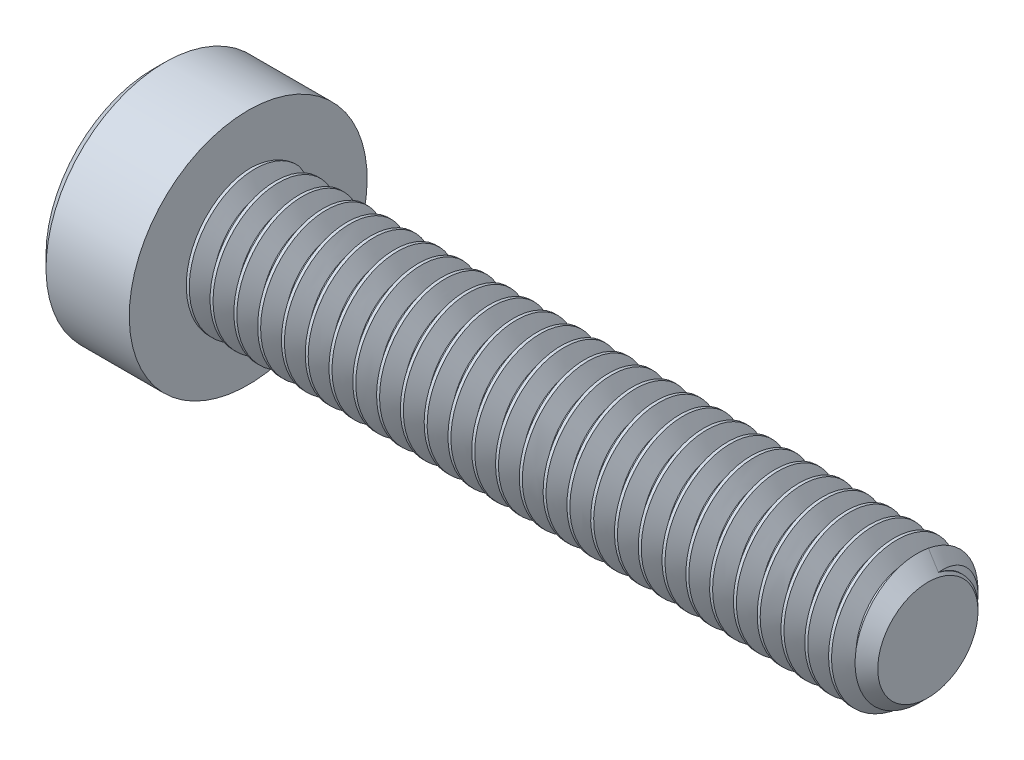
SolidWorks part; units mm, degrees
ref_plane "Front Plane" through (0, 0, 0) normal (0, 0, 1) x (1, 0, 0)
ref_plane "Top Plane" through (0, 0, 0) normal (0, 1, 0) x (1, 0, 0)
ref_plane "Right Plane" through (0, 0, 0) normal (1, 0, 0) x (0, 0, -1)
sketch "Sketch1" plane through (0, 0, 0) normal (0, 0, 1) x (1, 0, 0)
  line L0 (10, 0) -> (-10, 0) construction
  line L1 (10, 2) -> (10, -2) construction
  line L2 (-10, 3.5) -> (-10, -3.5) construction
  line L3 (-10, 3.5) -> (-12.45, 3.5) construction
  line L4 (-12.45, 3.5) -> (-12.8, 3.15) construction
  line L5 (-12.8, 3.15) -> (-12.8, -3.15) construction
  line L6 (-12.8, -3.15) -> (-12.45, -3.5) construction
  line L7 (-12.45, -3.5) -> (-10, -3.5) construction
  point P7 (-10.38, 0)
  point P12 (7.2, -2)
  dimension "D1" = 45
  dimension "Dec." = 4
  dimension "Length" = 20
  dimension "Head Dia" = 7
  dimension "Head Height" = 2.8
  dimension "Hex Depth" = 2.42
  dimension "Chamfer" = 0.35
  dimension "D2" = 2.8
ref_plane "Plane1" through (10, 0, 0) normal (1, 0, 0) x (0, 0, -1)
ref_plane "Plane2" through (-12.8, 0, 0) normal (1, 0, 0) x (0, 0, -1)
sketch "Sketch2" plane through (10, 0, 0) normal (1, 0, 0) x (0, 0, -1)
  circle A0 centre (0, 0) radius 2
extrude "Boss-Extrude1" add sketch "Sketch2" against normal up to vertex (20 mm away) up to point (-10, 0, 0)
sketch "Sketch3" plane through (10, 0, 0) normal (1, 0, 0) x (0, 0, -1)
  circle A0 centre (0, 0) radius 2 construction
  circle A1 centre (0, 0) radius 2
curve "Helix/Spiral1" pitch 0.7 height 20.6688 turns 29.5268 parameters "Pitch"=0.7
chamfer "Chamfer1" distance 0.525 angle 45 1 edges at (10, 0, -2)
sketch "Sketch5" plane through (0, 0, 0) normal (0, 0, 1) x (1, 0, 0)
  line L0 (9.6938, 2) -> (10.3062, 2)
  line L1 (10.3062, 2) -> (10.0438, 1.5453)
  line L2 (10.0438, 1.5453) -> (9.9563, 1.5453)
  line L3 (9.9563, 1.5453) -> (9.6938, 2)
  line L4 (10, 1.5453) -> (10, 2) construction
  line L5 (9.825, 1.7727) -> (10.175, 1.7727) construction
  dimension "D1" = 60
  dimension "D2" = 0.35
  dimension "D3" = 0.0875
sweep "Cut-Sweep1" cut profiles "Sketch5" path "Helix/Spiral1" align with end faces yes
sketch "Sketch4" plane through (-12.8, 0, 0) normal (1, 0, 0) x (0, 0, -1)
  line L0 (-3.5, 0.7937) -> (3.5, 0.7937) construction
  line L1 (0, 1.4434) -> (-1.25, 0.7217)
  line L2 (-1.25, 0.7217) -> (-1.25, -0.7217)
  line L3 (-1.25, -0.7217) -> (0, -1.4434)
  line L4 (0, -1.4434) -> (1.25, -0.7217)
  line L5 (1.25, -0.7217) -> (1.25, 0.7217)
  line L6 (1.25, 0.7217) -> (0, 1.4434)
  line L7 (0, 0) -> (0, 0.7937) construction
  circle A0 centre (0, 0) radius 1.25 construction
  dimension "Hex Size" = 2.5
  dimension "D1" = 7
  dimension "D2" = 0.7937
sketch "Sketch6" plane through (0, 0, 0) normal (0, 0, 1) x (1, 0, 0)
  line L0 (-12.45, 3.5) -> (-12.8, 3.15) construction
  line L1 (-10, 3.5) -> (-12.45, 3.5) construction
  line L2 (-10, 3.5) -> (-10, -3.5) construction
  line L3 (-12.8, 3.15) -> (-12.8, -3.15) construction
  line L4 (-12.45, 3.5) -> (-12.8, 3.15)
  line L5 (-10, 3.5) -> (-12.45, 3.5)
  line L6 (-10, 3.5) -> (-10, 0)
  line L7 (-12.8, 3.15) -> (-12.8, 0)
  line L8 (-10, 0) -> (-12.8, 0) construction
  line L9 (-10, 0) -> (-12.8, 0)
revolve "Revolve1" add sketch "Sketch6" angle 360 about L8
extrude "Cut-Extrude1" cut sketch "Sketch4" along normal up to vertex (2.42 mm away) up to point (-10.38, 0, 0)
sketch "Sketch8" plane through (-12.8, 0, 0) normal (-1, 0, 0) x (0, 0, 1)
  circle A1 centre (0, 0) radius 1.4434
extrude "Cut-Extrude2" cut sketch "Sketch8" against normal through all draft 45
equation "\"D3@Helix/Spiral1\" = \"Length@Sketch1\"+\"Pitch@Helix/Spiral1\"-.03124578"
equation "\"D3@Sketch5\" = \"Pitch@Helix/Spiral1\"*.125"
equation "\"D2@Sketch5\" = \"Pitch@Helix/Spiral1\"*.50"
equation "\"D1@Chamfer1\" = \"Pitch@Helix/Spiral1\"*.75"
equation "\"D2@Sketch1\" = \"Pitch@Helix/Spiral1\"*4"
equation "\"D1@Sketch4\" = \"Head Dia@Sketch1\""
equation "\"Chamfer@Sketch1\" = \"Head Height@Sketch1\"/8"
